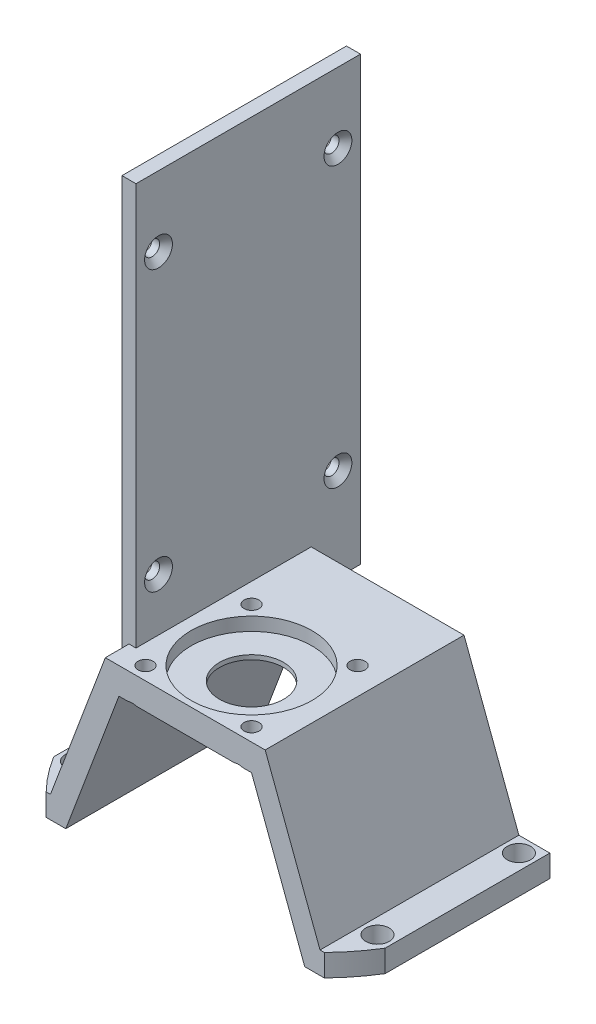
SolidWorks part; units mm, degrees
ref_plane "Front" through (0, 0, 0) normal (0, 0, 1) x (1, 0, 0)
ref_plane "Top" through (0, 0, 0) normal (0, 1, 0) x (1, 0, 0)
ref_plane "Right" through (0, 0, 0) normal (1, 0, 0) x (0, 0, -1)
sketch "Sketch1" plane through (0, 0, 0) normal (0, 0, 1) x (1, 0, 0)
  line L0 (37.5, 0) -> (-37.5, 0) construction
  line L1 (-37.5, 0) -> (-27.0389, 0)
  line L2 (37.5, 0) -> (27.0389, 0)
  line L3 (-37.5, 0) -> (-37.5, 5)
  line L4 (-37.5, 5) -> (-30.5, 5)
  line L5 (-30.5, 5) -> (-18.0848, 38)
  line L6 (-18.0848, 38) -> (18.0848, 38)
  line L7 (18.0848, 38) -> (30.5, 5)
  line L8 (30.5, 5) -> (37.5, 5)
  line L9 (37.5, 5) -> (37.5, 0)
  line L10 (-27.0389, 0) -> (-15, 32)
  line L11 (-15, 32) -> (15, 32)
  line L12 (15, 32) -> (27.0389, 0)
  point P4 (0, 0)
  dimension "D1" = 75
  dimension "D2" = 5
  dimension "D3" = 7
  dimension "D4" = 5
  dimension "D5" = 38
  dimension "D6" = 30
  dimension "D7" = 6
extrude "Boss-Extrude1" add sketch "Sketch1" along normal blind 45
sketch "Sketch2" plane through (0, 38, 0) normal (0, 1, 0) x (1, 0, 0)
  line L0 (0, 0) -> (0, -30) construction
  line L2 (12, -42) -> (-12, -42) construction
  line L3 (12, -42) -> (12, -18) construction
  line L4 (12, -18) -> (-12, -18) construction
  line L5 (-12, -42) -> (-12, -18) construction
  line L6 (12, -42) -> (-12, -18) construction
  line L7 (12, -18) -> (-12, -42) construction
  dimension "D1" = 30
  dimension "D2" = 24
sketch "Sketch3" plane through (0, 38, 0) normal (0, 1, 0) x (1, 0, 0)
  line L0 (12, -18) -> (-12, -42) construction
  circle A0 centre (0, -30) radius 13.7
  dimension "D1" = 27.4
extrude "Cut-Extrude1" cut sketch "Sketch3" against normal blind 3
hole_wizard "CSK for M3 Flat Head Machine Screw4" positions "Sketch5" profile "Sketch6" countersink size "M3" standard "ANSI Metric" end condition through all
sketch "Sketch5" plane through (0, 32, 0) normal (0, -1, 0) x (-1, 0, 0)
  point P0 (12, -42)
  point P3 (-12, -42)
  point P6 (-12, -18)
  point P9 (12, -18)
sketch "Sketch6" plane through (-12, 32, 42) normal (1, 0, 0) x (0, 0, -1)
  line L0 (0, 0) -> (0, 6)
  line L1 (0, 6) -> (1.7, 6)
  line L2 (1.7, 6) -> (1.7, 1.45)
  line L3 (1.7, 1.45) -> (3.15, 0)
  line L5 (3.15, 0) -> (0, 0)
  line L6 (-1.7, 1.45) -> (-3.15, 0) construction
  line L11 (0, -6.35) -> (0, 107.95) construction
  dimension "Thru Hole Dia." = 3.4
  dimension "Thru Hole Depth" = 6
  dimension "Near C'Sink Dia." = 6.3
  dimension "Near C'Sink Angle" = 90
sketch "Sketch10" plane through (0, 35, 0) normal (0, 1, 0) x (1, 0, 0)
  circle A0 centre (0, -30) radius 7.25
  dimension "D1" = 14.5
extrude "Cut-Extrude2" cut sketch "Sketch10" against normal through all
sketch "Sketch15" plane through (0, 38, 0) normal (0, 1, 0) x (1, 0, 0)
  line L0 (0, -30) -> (0, -14.25) construction
  circle A0 centre (0, -14.25) radius 44
  circle A1 centre (0, -14.25) radius 48.4955
  dimension "D2" = 88
  dimension "D1" = 15.75
extrude "Cut-Extrude4" cut sketch "Sketch15" against normal through all
sketch "Sketch11" plane through (0, 32, 0) normal (0, -1, 0) x (1, 0, 0)
  circle A0 centre (0, 30) radius 10.5
  dimension "D1" = 21
extrude "Cut-Extrude3" cut sketch "Sketch11" against normal blind 2
sketch "Sketch7" plane through (0, 0, 0) normal (0, -1, 0) x (1, 0, 0)
  line L0 (0, 19.5) -> (0, 0) construction
  line L1 (-30.5, 35.5) -> (-37.5, 35.5) construction
  line L2 (-34, 3.5) -> (34, 3.5) construction
  line L3 (-34, 3.5) -> (-34, 35.5) construction
  line L4 (-34, 35.5) -> (34, 35.5) construction
  line L5 (34, 3.5) -> (34, 35.5) construction
  line L6 (-34, 3.5) -> (34, 35.5) construction
  line L7 (-34, 35.5) -> (34, 3.5) construction
  line L8 (-30.5, 45) -> (-30.5, 0) construction
  line L9 (-37.5, 37.2663) -> (-37.5, 0) construction
  line L12 (-37.5, 0) -> (-27.0389, 0) construction
  point P4 (0, 19.5)
  point P5 (0, 19.5)
  point P16 (-34, 35.5)
  dimension "D1" = 3.5
  dimension "D2" = 32
hole_wizard "CBORE for M5 Hex Head Bolt1" positions "Sketch13" profile "Sketch14" counterbore size "M5" standard "ANSI Metric" end condition through all
sketch "Sketch13" plane through (0, 5, 0) normal (0, -1, 0) x (-1, 0, 0)
  point P0 (34, -35.5)
  point P3 (34, -3.5)
  point P6 (-34, -3.5)
  point P9 (-34, -35.5)
sketch "Sketch14" plane through (-34, 5, 35.5) normal (1, 0, 0) x (0, 0, 1)
  line L0 (0, 0) -> (0, 5)
  line L1 (0, 5) -> (1.7, 5)
  line L3 (1.7, 5) -> (1.7, 4)
  line L4 (1.7, 4) -> (2.65, 4)
  line L5 (2.65, 4) -> (2.65, 0)
  line L7 (2.65, 0) -> (0, 0)
  line L11 (0, -6.35) -> (0, 107.95) construction
  dimension "Thru Hole Dia." = 3.4
  dimension "Thru Hole Depth" = 5
  dimension "C'Bore Dia." = 5.3
  dimension "C'Bore Depth" = 4
sketch "Sketch19" plane through (0, 38, 0) normal (0, 1, 0) x (1, 0, 0)
  line L0 (18.0848, 0) -> (-18.0848, 0) construction
  line L1 (-25.4, -10) -> (25.4, -10)
  line L2 (-25.4, -10) -> (-25.4, -13.175)
  line L3 (-25.4, -13.175) -> (25.4, -13.175)
  line L4 (25.4, -10) -> (25.4, -13.175)
  point P6 (0, 0)
  point P7 (0, -10)
  dimension "D1" = 3.175
  dimension "D2" = 50.8
  dimension "D3" = 10
extrude "Boss-Extrude5" [suppressed] add sketch "Sketch19" along normal blind 100
fillet "Fillet2" [suppressed] radius 8
fillet "Fillet3" [suppressed] radius 8
sketch "Sketch20" [suppressed] plane through (0, 0, 13.175) normal (0, 0, -1) x (-1, 0, 0)
  line L1 (20.3, 58.9) -> (-20.3, 58.9)
  line L2 (20.3, 58.9) -> (20.3, 122.1)
  line L3 (20.3, 122.1) -> (-20.3, 122.1)
  line L4 (-20.3, 58.9) -> (-20.3, 122.1)
  line L5 (-25.4, 138) -> (25.4, 138) construction
  point P7 (-20.3, 90.5)
  point P8 (0, 122.1)
  point P11 (0, 138)
  dimension "D1" = 40.6
  dimension "D2" = 63.2
  dimension "D3" = 47.5
hole_wizard "CSK for M3 Flat Head Machine Screw2" [suppressed] positions "Sketch26" profile "Sketch27" countersink size "M3" standard "ANSI Metric"
sketch "Sketch26" [suppressed] plane through (0, 0, 13.175) normal (0, 0, 1) x (1, 0, 0)
  point P0 (20.3, 58.9)
  point P3 (20.3, 122.1)
  point P6 (-20.3, 122.1)
  point P9 (-20.3, 58.9)
sketch "Sketch27" plane through (20.3, 58.9, 13.175) normal (1, 0, 0) x (0, -1, 0)
  line L0 (0, 0) -> (0, 13.175)
  line L1 (0, 13.175) -> (1.7, 13.175)
  line L2 (1.7, 13.175) -> (1.7, 1.45)
  line L3 (1.7, 1.45) -> (3.15, 0)
  line L5 (3.15, 0) -> (0, 0)
  line L6 (-1.7, 1.45) -> (-3.15, 0) construction
  line L11 (0, -6.35) -> (0, 107.95) construction
  dimension "Thru Hole Dia." = 3.4
  dimension "Thru Hole Depth" = 13.175
  dimension "Near C'Sink Dia." = 6.3
  dimension "Near C'Sink Angle" = 90
ref_plane "Plane1" through (-18.0848, 0, 0) normal (1, 0, 0) x (0, 0, -1)
ref_plane "Plane2" through (-18.0848, 0, 0) normal (1, 0, 0) x (0, 0, -1)
ref_point "Point1"
sketch "Sketch28" plane through (-18.0848, 0, 0) normal (1, 0, 0) x (0, 0, -1)
  line L0 (-45, 38) -> (0, 38) construction
  line L1 (-39.65, 29) -> (11.15, 29)
  line L2 (-39.65, 29) -> (-39.65, 129)
  line L3 (-39.65, 129) -> (11.15, 129)
  line L4 (11.15, 29) -> (11.15, 129)
  point P4 (-14.25, 0)
  point P7 (-14.25, 29)
  dimension "D1" = 50.8
  dimension "D2" = 100
  dimension "D3" = 91
extrude "Boss-Extrude6" add sketch "Sketch28" along normal blind 1.5875 and the other way blind 1.5875 contours L4 L3 L2 L1
fillet "Fillet4" radius 9 1 edges at (-18.0848, 29, 0)
sketch "Sketch29" plane through (-16.4973, 0, 0) normal (-1, 0, 0) x (0, 0, 1)
  line L0 (39.65, 129) -> (-11.15, 129) construction
  line L1 (34.55, 49.9) -> (-6.05, 49.9)
  line L2 (34.55, 49.9) -> (34.55, 113.1)
  line L3 (34.55, 113.1) -> (-6.05, 113.1)
  line L4 (-6.05, 49.9) -> (-6.05, 113.1)
  point P4 (14.25, 49.9)
  point P7 (14.25, 129)
  point P8 (-6.05, 81.5)
  dimension "D1" = 63.2
  dimension "D2" = 40.6
  dimension "D3" = 47.5
hole_wizard "CSK for M3 Flat Head Machine Screw3" positions "Sketch30" profile "Sketch31" countersink size "M3" standard "ANSI Metric" end condition through all
sketch "Sketch30" plane through (-16.4973, 0, 0) normal (1, 0, 0) x (0, 0, -1)
  point P0 (6.05, 49.9)
  point P3 (-34.55, 49.9)
  point P6 (-34.55, 113.1)
  point P9 (6.05, 113.1)
sketch "Sketch31" plane through (-16.4973, 49.9, -6.05) normal (0, 1, 0) x (0, 0, -1)
  line L0 (0, 0) -> (0, 21.0027)
  line L1 (0, 21.0027) -> (1.7, 21.0027)
  line L2 (1.7, 21.0027) -> (1.7, 1.45)
  line L3 (1.7, 1.45) -> (3.15, 0)
  line L5 (3.15, 0) -> (0, 0)
  line L6 (-1.7, 1.45) -> (-3.15, 0) construction
  line L11 (0, -6.35) -> (0, 107.95) construction
  dimension "Thru Hole Dia." = 3.4
  dimension "Thru Hole Depth" = 21.0027
  dimension "Near C'Sink Dia." = 6.3
  dimension "Near C'Sink Angle" = 90
sketch "Sketch32" plane through (-19.6723, 0, 0) normal (-1, 0, 0) x (0, 0, 1)
  line L1 (-11.15, 29) -> (39.65, 29)
  line L2 (-11.15, 29) -> (-11.15, 33.7804)
  line L3 (-11.15, 33.7804) -> (39.65, 33.7804)
  line L4 (39.65, 29) -> (39.65, 33.7804)
extrude "Cut-Extrude5" cut sketch "Sketch32" along normal blind 3.175
